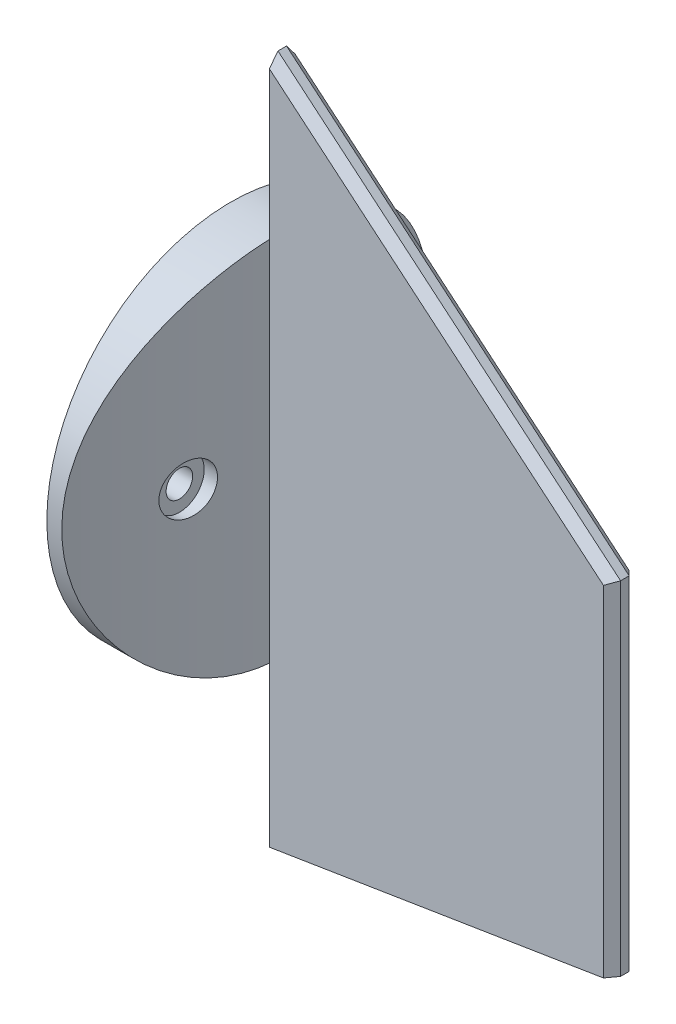
SolidWorks part; units mm, degrees
ref_plane "Front Plane" through (0, 0, 0) normal (0, 0, 1) x (1, 0, 0)
ref_plane "Top Plane" through (0, 0, 0) normal (0, 1, 0) x (1, 0, 0)
ref_plane "Right Plane" through (0, 0, 0) normal (1, 0, 0) x (0, 0, -1)
sketch "Sketch13" plane through (0, 0, 0) normal (1, 0, 0) x (0, 0, -1)
  line L0 (-2.6217, -2.2425) -> (-1.8172, -14.1833)
  line L1 (2.1766, -14.1326) -> (2.6778, -2.1753)
  arc A0 (2.6778, -2.1753) -> (-2.6217, -2.2425) centre (0, 0) ccw
  arc A1 (-1.8172, -14.1833) -> (2.1766, -14.1326) centre (0.1783, -14.0489) ccw
  circle A2 centre (0, 0) radius 16.3675
  dimension "D1" = 3.45
  dimension "D2" = 2
  dimension "D6" = 32.735
  dimension "D3" = 0.1783
  dimension "D4" = 2.1766
  dimension "D5" = 2.6778
extrude "Boss-Extrude11" add sketch "Sketch13" along normal mid plane 1.524
sketch "Sketch14" plane through (0.762, 0, 0) normal (1, 0, 0) x (0, 0, -1)
  circle A0 centre (0, 0) radius 16.3675
  circle A1 centre (0, 0) radius 16.3675 construction
extrude "Boss-Extrude12" add sketch "Sketch14" along normal mid plane 1.016
sketch "Sketch15" plane through (0, 0, 0) normal (0, 0, 1) x (1, 0, 0)
  line L0 (1.27, 18.3324) -> (1.27, -21.3321) construction
  line L1 (1.27, 0) -> (1.27, 25.4)
  line L2 (1.27, -16.3675) -> (1.27, 16.3675) construction
  line L3 (1.27, 0) -> (1.27, -25.4)
  line L4 (1.27, -25.4) -> (26.67, -21.3131)
  line L5 (26.67, -21.3131) -> (26.67, 4.0869)
  line L6 (26.67, 4.0869) -> (1.27, 25.4)
  dimension "D1" = 50
  dimension "D2" = 25.4
  dimension "D3" = 25.4
  dimension "D4" = 25.4
  dimension "D5" = 25.4
extrude "Boss-Extrude13" add sketch "Sketch15" along normal mid plane 1.905
fillet "Chamfer6" radius 0.762 4 edges at (13.97, 14.7434, -0.9525) (26.67, -8.6131, -0.9525) (26.67, -8.6131, 0.9525) (13.97, 14.7434, 0.9525) profile chamfer
sketch "Sketch20" plane through (-0.762, 0, 0) normal (-1, 0, 0) x (0, 0, 1)
  line L2 (1.8172, -14.1833) -> (2.6217, -2.2425)
  line L3 (-2.6778, -2.1753) -> (-2.1766, -14.1326)
  line L4 (1.8172, -14.1833) -> (2.6217, -2.2425)
  line L5 (-2.6778, -2.1753) -> (-2.1766, -14.1326)
  circle A1 centre (0, 0) radius 16.3675
  circle A2 centre (0, 0) radius 16.3675
  arc A4 (2.6217, -2.2425) -> (-2.6778, -2.1753) centre (0, 0) ccw
  arc A5 (-2.1766, -14.1326) -> (1.8172, -14.1833) centre (-0.1783, -14.0489) ccw
  arc A6 (2.6217, -2.2425) -> (-2.6778, -2.1753) centre (0, 0) ccw
  arc A7 (-2.1766, -14.1326) -> (1.8172, -14.1833) centre (-0.1783, -14.0489) ccw
  dimension "D1" = 0
  dimension "D2" = 0
sketch "Sketch26" plane through (0.254, 0, 0) normal (-1, 0, 0) x (0, 0, 1)
  line L2 (-2.6778, -2.1753) -> (-2.1766, -14.1326)
  line L3 (1.8172, -14.1833) -> (2.6217, -2.2425)
  line L4 (-2.6778, -2.1753) -> (-2.1766, -14.1326)
  line L5 (1.8172, -14.1833) -> (2.6217, -2.2425)
  arc A2 (2.6217, -2.2425) -> (-2.6778, -2.1753) centre (0, 0) ccw
  arc A3 (-2.1766, -14.1326) -> (1.8172, -14.1833) centre (-0.1783, -14.0489) ccw
  arc A4 (2.6217, -2.2425) -> (-2.6778, -2.1753) centre (0, 0) ccw
  arc A5 (-2.1766, -14.1326) -> (1.8172, -14.1833) centre (-0.1783, -14.0489) ccw
  dimension "D1" = 0
extrude "Boss-Extrude19" add sketch "Sketch26" along normal up to surface (1.016 mm away) up to face at (-0.762, 0, -16.3675)
sketch "Sketch27" plane through (1.27, 0, 0) normal (1, 0, 0) x (0, 0, -1)
  line L1 (0.9525, 16.3398) -> (0.9525, -16.3398)
  line L3 (0.9525, 16.3398) -> (0.9525, -16.3398)
  line L5 (-0.9525, -16.3398) -> (-0.9525, 16.3398)
  line L6 (-0.9525, -16.3398) -> (-0.9525, 16.3398)
  arc A1 (0.9525, -16.3398) -> (0.9525, 16.3398) centre (0, 0) ccw
  arc A2 (0.9525, -16.3398) -> (0.9525, 16.3398) centre (0, 0) ccw
  arc A3 (-0.9525, 16.3398) -> (-0.9525, -16.3398) centre (0, 0) ccw
  arc A4 (-0.9525, 16.3398) -> (-0.9525, -16.3398) centre (0, 0) ccw
  dimension "D1" = 0
  dimension "D2" = 0
extrude "Boss-Extrude20" add sketch "Sketch27" along normal blind 1.524
sketch "Sketch28" plane through (2.794, 0, 0) normal (1, 0, 0) x (0, 0, -1)
  line L0 (-23.2899, 0) -> (37.7845, 0) construction
  line L1 (-16.3675, 18.2766) -> (-16.3675, 10.7478) construction
  line L2 (0, 0) -> (0, -28.4596) construction
  circle A0 centre (-7.6248, 0) radius 2.2098
  arc A1 (-0.9525, 16.3398) -> (-0.9525, -16.3398) centre (0, 0) ccw construction
  circle A2 centre (7.6248, 0) radius 2.2098
  dimension "D1" = 4.4196
  dimension "D2" = 8.7427
extrude "Cut-Extrude9" cut sketch "Sketch28" against normal blind 1.524
sketch "Sketch29" plane through (1.27, 0, 0) normal (1, 0, 0) x (0, 0, -1)
  circle A0 centre (-7.6248, 0) radius 1.1811
  circle A1 centre (7.6248, 0) radius 1.1811
  dimension "D1" = 2.3622
  dimension "D2" = 2.3622
extrude "Cut-Extrude10" cut sketch "Sketch29" against normal blind 14.224
sketch "Sketch31" plane through (2.794, 0, 0) normal (1, 0, 0) x (0, 0, -1)
  line L0 (0.9525, 16.3398) -> (0.9525, -16.3398) construction
  line L1 (-0.9525, -16.3398) -> (-0.9525, 16.3398) construction
  line L2 (0.9525, 16.3398) -> (0.9525, -16.3398)
  line L3 (-0.9525, -16.3398) -> (-0.9525, 16.3398)
  circle A0 centre (7.6248, 0) radius 2.2098 construction
  circle A1 centre (-7.6248, 0) radius 2.2098
  circle A2 centre (-7.6248, 0) radius 2.2098
  circle A3 centre (7.6248, 0) radius 2.2098
  arc A4 (0.9525, -16.3398) -> (0.9525, 16.3398) centre (0, 0) ccw construction
  arc A5 (-0.9525, 16.3398) -> (-0.9525, -16.3398) centre (0, 0) ccw construction
  arc A6 (0.9525, -16.3398) -> (0.9525, 16.3398) centre (0, 0) ccw
  arc A7 (-0.9525, 16.3398) -> (-0.9525, -16.3398) centre (0, 0) ccw
  dimension "D1" = 0
sketch "Sketch32" plane through (-0.762, 0, 0) normal (-1, 0, 0) x (0, 0, 1)
  circle A0 centre (-7.6248, 0) radius 1.1811 construction
  circle A1 centre (-7.6248, 0) radius 1.1811
  circle A2 centre (7.6248, 0) radius 1.1811 construction
  circle A3 centre (7.6248, 0) radius 1.1811
  circle A5 centre (0, 0) radius 16.3675
  circle A6 centre (0, 0) radius 16.3675
  dimension "D1" = 0
sketch "Sketch35" plane through (2.794, 0, 0) normal (1, 0, 0) x (0, 0, -1)
  circle A0 centre (0, 0) radius 16.3675
  circle A1 centre (0, 0) radius 32.2294
extrude "Cut-Extrude15" cut sketch "Sketch35" along normal blind 52.832 contours A0
sketch "Sketch36" plane through (2.794, 0, 0) normal (1, 0, 0) x (0, 0, -1)
  circle A0 centre (0, 0) radius 29.1724
  circle A1 centre (0, 0) radius 16.3675
extrude "Cut-Extrude16" cut sketch "Sketch36" against normal blind 52.832 and the other way blind 52.832
sketch "Sketch33" plane through (0, 0, 0) normal (0, 1, 0) x (1, 0, 0)
  line L0 (-3.8217, 0) -> (38.6284, 0) construction
  line L2 (2.794, -16.3675) -> (2.794, 16.3675) construction
  line L3 (2.794, 16.3675) -> (-0.762, 16.3675) construction
  line L4 (-0.4519, 16.3675) -> (-0.762, 16.3675)
  line L5 (-0.4519, 16.3675) -> (-0.4519, -16.3675)
  line L6 (-0.4519, -16.3675) -> (-0.762, -16.3675)
  line L7 (-0.762, 16.3675) -> (-0.762, -16.3675)
  line L9 (-0.4519, 16.3675) -> (2.794, 16.3675)
  line L10 (-0.4519, 16.3675) -> (-0.4519, -16.3675)
  line L11 (-0.4519, -16.3675) -> (2.794, -16.3675)
  line L12 (2.794, 16.3675) -> (2.794, -16.3675)
  circle A0 centre (-40.0958, 0) radius 42.8898
  dimension "D1" = 85.7797
extrude "Cut-Extrude17" cut sketch "Sketch33" against normal blind 52.832 and the other way blind 52.832 contours A0 L11 L12 | A0 L12 L9 region at (1.8269, 0, -12.3072) region at (1.8269, 0, 12.3072)
ref_plane "Plane6" through (0, 0, 0) normal (0, 0, -1) x (-1, 0, 0)
sketch "Sketch38" plane through (0, 0, 0) normal (0, 0, -1) x (-1, 0, 0)
  line L0 (-2.794, 0) -> (-2.794, 30.48)
  line L1 (-2.794, 16.3675) -> (-2.794, -16.3675) construction
  line L2 (-2.794, 30.48) -> (-2.794, 0)
  line L3 (-2.794, 0) -> (-2.794, -30.48)
  line L4 (-2.794, -30.48) -> (-33.274, -25.5758)
  line L5 (-33.274, -25.5758) -> (-33.274, 4.9042)
  line L6 (-33.274, 4.9042) -> (-2.794, 30.48)
  line L7 (-2.794, 30.48) -> (-38.6624, 30.48) construction
  dimension "D1" = 30.48
  dimension "D2" = 30.48
  dimension "D3" = 40
  dimension "D4" = 30.48
  dimension "D5" = 30.48
extrude "Boss-Extrude21" add sketch "Sketch38" along normal mid plane 2.286 separate body contours L6 L5 L4 L3 L0 region at (16.3407, -4.5937, 0)
fillet "Chamfer7" radius 0.762 4 edges at (33.274, -10.3358, 1.143) (33.274, -10.3358, -1.143) (18.034, 17.6921, -1.143) (18.034, 17.6921, 1.143) profile chamfer
sketch "Sketch39" plane through (-0.762, 0, 0) normal (-1, 0, 0) x (0, 0, 1)
  circle A1 centre (0, 0) radius 16.3675
  circle A2 centre (0, 0) radius 16.3675
  dimension "D1" = 0
sketch "Sketch41" plane through (-0.762, 0, 0) normal (-1, 0, 0) x (0, 0, 1)
  circle A0 centre (0, 0) radius 2.921
  circle A1 centre (0, 0) radius 16.3675
  circle A2 centre (0, 0) radius 16.3675
  dimension "D2" = 5.842
  dimension "D1" = 0
extrude "Cut-Extrude19" cut sketch "Sketch41" against normal blind 1.524 contours A0 region at (-0.762, 0, 0)
sketch "Sketch42" plane through (-0.762, 0, 0) normal (-1, 0, 0) x (0, 0, 1)
  circle A0 centre (0, 0) radius 4.064
  dimension "D1" = 8.128
extrude "Cut-Extrude20" cut sketch "Sketch42" against normal mid plane 1.524
sketch "Sketch43" plane through (0.762, 0, 0) normal (-1, 0, 0) x (0, 0, 1)
  circle A1 centre (0, 0) radius 2.921
  circle A2 centre (0, 0) radius 2.921
  dimension "D1" = 0
extrude "Cut-Extrude21" cut sketch "Sketch43" against normal mid plane 1.016
sketch "Sketch44" plane through (0, 0, 0) normal (-1, 0, 0) x (0, 0, 1)
  circle A3 centre (0, 0) radius 5.4102
  point P1 (-13.1272, -0.9257)
  point P7 (-25.1158, -0.1986)
  dimension "D3" = 10.8204
extrude "Cut-Extrude24" cut sketch "Sketch44" against normal blind 0.9398 and the other way blind 0.9398
sketch "Sketch46" plane through (1.27, 0, 0) normal (-1, 0, 0) x (0, 0, 1)
  circle A1 centre (0, 0) radius 2.921
  circle A2 centre (0, 0) radius 2.921
  dimension "D1" = 0
extrude "Cut-Extrude25" cut sketch "Sketch46" against normal blind 0.508
sketch "Sketch47" plane through (-0.762, 0, 0) normal (-1, 0, 0) x (0, 0, 1)
  circle A0 centre (7.6248, 0) radius 1.1811 construction
  circle A1 centre (0, 0) radius 16.3675
  circle A2 centre (0, 0) radius 16.3675
  circle A3 centre (-7.6248, 0) radius 1.1811 construction
  circle A4 centre (0, 0) radius 5.4102 construction
  circle A5 centre (7.6248, 0) radius 1.1811
  circle A6 centre (-7.6248, 0) radius 1.1811
  circle A7 centre (0, 0) radius 5.4102
  dimension "D1" = 0
extrude "Boss-Extrude22" add sketch "Sketch47" along normal blind 1.016
sketch "Sketch48" plane through (0.9398, 0, 0) normal (-1, 0, 0) x (0, 0, 1)
  circle A0 centre (0, 0) radius 2.921 construction
  circle A1 centre (0, 0) radius 5.4102
  circle A2 centre (0, 0) radius 5.4102
  circle A3 centre (0, 0) radius 2.921
  dimension "D1" = 0
extrude "Boss-Extrude23" add sketch "Sketch48" along normal blind 1.524
sketch "Sketch49" plane through (1.778, 0, 0) normal (-1, 0, 0) x (0, 0, 1)
  circle A1 centre (0, 0) radius 2.921
  circle A2 centre (0, 0) radius 2.921
  dimension "D1" = 0
extrude "Boss-Extrude24" add sketch "Sketch49" along normal blind 0.762
sketch "Sketch51" plane through (-0.5842, 0, 0) normal (-1, 0, 0) x (0, 0, 1)
  circle A1 centre (0, 0) radius 5.4102
  circle A2 centre (0, 0) radius 5.4102
  dimension "D1" = 0
extrude "Cut-Extrude26" cut sketch "Sketch51" against normal up to surface (1.6002 mm away) up to face at (1.016, 0, 2.921)
sketch "Sketch53" plane through (0, 0, 0) normal (1, 0, 0) x (0, 0, -1)
  circle A0 centre (-7.6248, 0) radius 2.2098
sketch "Sketch17" plane through (0, 0, 0) normal (0, 1, 0) x (1, 0, 0)
  line L0 (2.7484, 0) -> (76.4286, 0) construction
  line L1 (1.27, -0.1905) -> (1.27, 0.1905) construction
  line L3 (-0.762, 16.3675) -> (1.27, 16.3675)
  line L4 (-0.762, 16.3675) -> (-0.762, -16.3675)
  line L5 (-0.4519, 0) -> (-0.762, 0) construction
  line L6 (-0.762, -16.3675) -> (1.27, -16.3675)
  line L7 (1.27, 16.3675) -> (1.27, -16.3675)
  circle A0 centre (-38.5818, 0) radius 39.8518
  point P3 (1.27, 0)
  dimension "D1" = 79.7036
extrude "Cut-Extrude5" [suppressed] cut sketch "Sketch17" against normal mid plane 50.8 contours A0 L4 L6 L7 | A0 L7 L3 L4
sketch "Sketch18" plane through (-0.762, 0, 0) normal (-1, 0, 0) x (0, 0, 1)
  line L0 (-2.803, -2.2222) -> (-2.3035, -14.138)
  line L1 (1.9439, -14.1919) -> (2.7457, -2.2927)
  line L2 (-2.6778, -2.1753) -> (-2.1766, -14.1326)
  line L3 (1.8172, -14.1833) -> (2.6217, -2.2425)
  line L4 (-2.6778, -2.1753) -> (-2.1766, -14.1326)
  line L5 (1.8172, -14.1833) -> (2.6217, -2.2425)
  arc A0 (2.7457, -2.2927) -> (-2.803, -2.2222) centre (0, 0) ccw
  arc A1 (-2.3035, -14.138) -> (1.9439, -14.1919) centre (-0.1783, -14.0489) ccw
  arc A2 (2.6217, -2.2425) -> (-2.6778, -2.1753) centre (0, 0) ccw
  arc A3 (-2.1766, -14.1326) -> (1.8172, -14.1833) centre (-0.1783, -14.0489) ccw
  arc A4 (2.6217, -2.2425) -> (-2.6778, -2.1753) centre (0, 0) ccw
  arc A5 (-2.1766, -14.1326) -> (1.8172, -14.1833) centre (-0.1783, -14.0489) ccw
  dimension "D1" = 0
  dimension "D2" = 0.127
extrude "Cut-Extrude6" [suppressed] cut sketch "Sketch18" against normal up to surface (1.016 mm away)
sketch "Sketch19" [suppressed] plane through (-0.762, 0, 0) normal (-1, 0, 0) x (0, 0, 1)
  line L2 (-12.563, 10.4913) -> (-12.563, -10.4913)
  line L3 (12.563, -10.4913) -> (12.563, 10.4913)
  line L4 (-12.563, 10.4913) -> (-12.563, -10.4913)
  line L5 (12.563, -10.4913) -> (12.563, 10.4913)
  line L6 (-2.803, -2.2222) -> (-2.3035, -14.138)
  line L7 (1.9439, -14.1919) -> (2.7457, -2.2927)
  line L8 (-2.803, -2.2222) -> (-2.3035, -14.138)
  line L9 (1.9439, -14.1919) -> (2.7457, -2.2927)
  arc A2 (-12.563, -10.4913) -> (12.563, -10.4913) centre (0, 0) ccw
  arc A3 (12.563, 10.4913) -> (-12.563, 10.4913) centre (0, 0) ccw
  arc A4 (-12.563, -10.4913) -> (12.563, -10.4913) centre (0, 0) ccw
  arc A5 (12.563, 10.4913) -> (-12.563, 10.4913) centre (0, 0) ccw
  arc A6 (2.7457, -2.2927) -> (-2.803, -2.2222) centre (0, 0) ccw
  arc A7 (-2.3035, -14.138) -> (1.9439, -14.1919) centre (-0.1783, -14.0489) ccw
  arc A8 (2.7457, -2.2927) -> (-2.803, -2.2222) centre (0, 0) ccw
  arc A9 (-2.3035, -14.138) -> (1.9439, -14.1919) centre (-0.1783, -14.0489) ccw
  dimension "D1" = 0
  dimension "D2" = 0
extrude "Boss-Extrude15" [suppressed] add sketch "Sketch19" along normal blind 2.54
